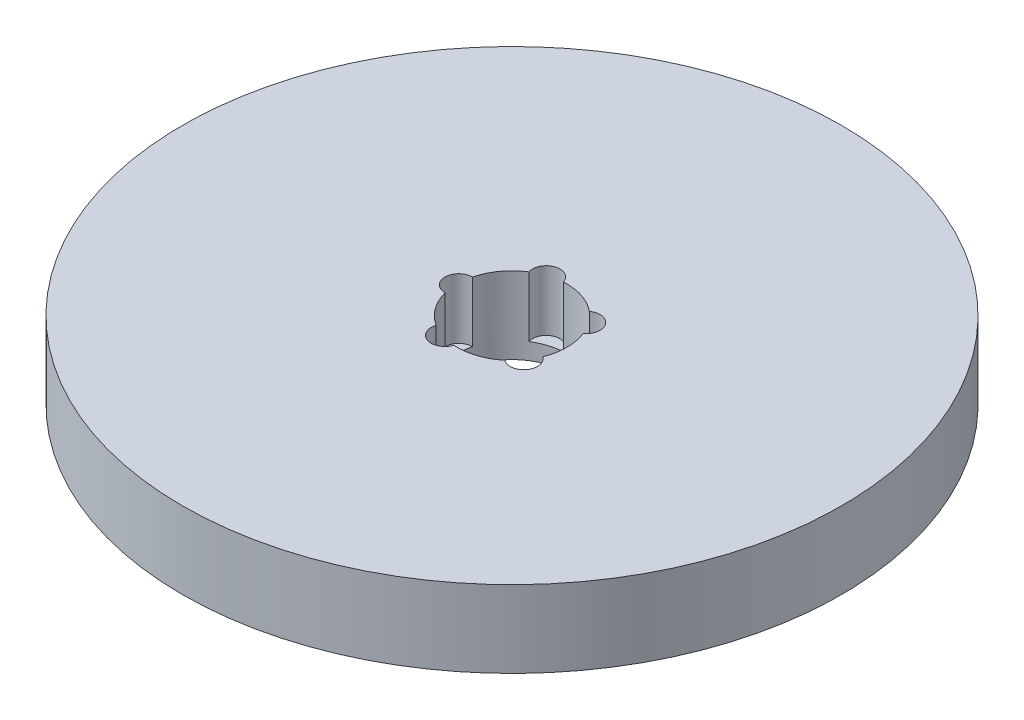
SolidWorks part; units mm, degrees
ref_plane "Front Plane" through (0, 0, 0) normal (0, 0, 1) x (1, 0, 0)
ref_plane "Top Plane" through (0, 0, 0) normal (0, 1, 0) x (1, 0, 0)
ref_plane "Right Plane" through (0, 0, 0) normal (1, 0, 0) x (0, 0, -1)
sketch "Sketch1" plane through (0, 0, 0) normal (0, 1, 0) x (1, 0, 0)
  circle A0 centre (0, 0) radius 90
  dimension "FLANGE_OD" = 180
extrude "Boss-Extrude1" add sketch "Sketch1" along normal blind 21
sketch "Sketch2" plane through (0, 0, 0) normal (0, 1, 0) x (1, 0, 0)
  circle A0 centre (0, 0) radius 15
  dimension "BORE_D" = 30
extrude "Cut-Extrude1" cut sketch "Sketch2" along normal through all
sketch "Sketch3" plane through (0, 21, 0) normal (0, 1, 0) x (1, 0, 0)
  circle A0 centre (0, 0) radius 14.5501 construction
  circle A1 centre (-14.5501, 0) radius 3.7338
  dimension "BOLT_D" = 7.4677
  dimension "BOLT_PCD" = 29.1001
extrude "Cut-Extrude2" cut sketch "Sketch3" against normal blind 16.4873
pattern_circular "CirPattern1" count 5 over 360 about axis through (0, 0, 0) along (0, 1, 0) of "Cut-Extrude2"
